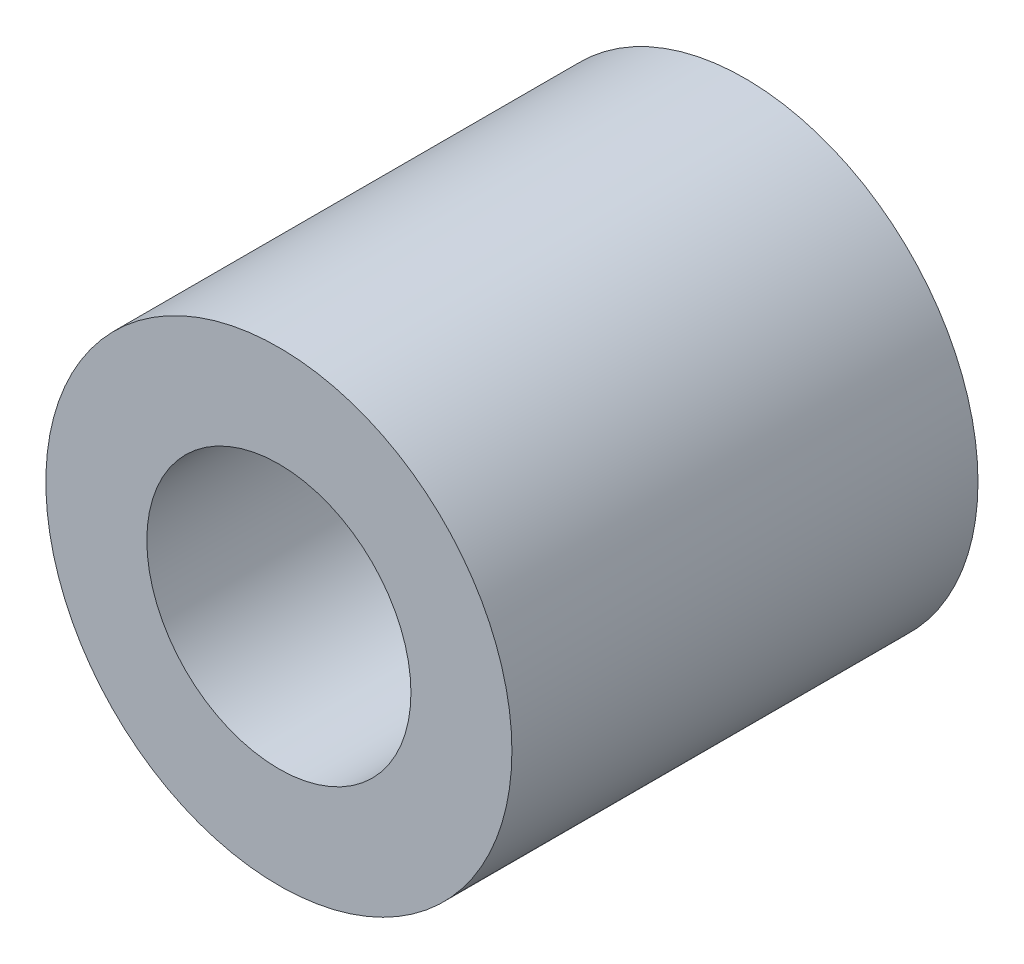
SolidWorks part; units mm, degrees
ref_plane "Front Plane" through (0, 0, 0) normal (0, 0, 1) x (1, 0, 0)
ref_plane "Top Plane" through (0, 0, 0) normal (0, 1, 0) x (1, 0, 0)
ref_plane "Right Plane" through (0, 0, 0) normal (1, 0, 0) x (0, 0, -1)
sketch "Sketch1" plane through (0, 0, 0) normal (0, 0, 1) x (1, 0, 0)
  circle A0 centre (0, 0) radius 3
extrude "Boss-Extrude1" add sketch "Sketch1" along normal blind 6
hole_wizard "M3 Clearance Hole1" positions "Sketch2" profile "Sketch3" hole size "M3" standard "ANSI Metric" end condition through all
sketch "Sketch2" plane through (0, 0, 6) normal (0, 0, 1) x (1, 0, 0)
  point P0 (0, 0)
sketch "Sketch3" plane through (0, 0, 6) normal (1, 0, 0) x (0, -1, 0)
  line L0 (0, 0) -> (0, 6)
  line L1 (0, 6) -> (1.7, 6)
  line L2 (1.7, 6) -> (1.7, 0)
  line L5 (1.7, 0) -> (0, 0)
  line L11 (0, -6.35) -> (0, 107.95) construction
  dimension "Thru Hole Dia." = 3.4
  dimension "Thru Hole Depth" = 6
